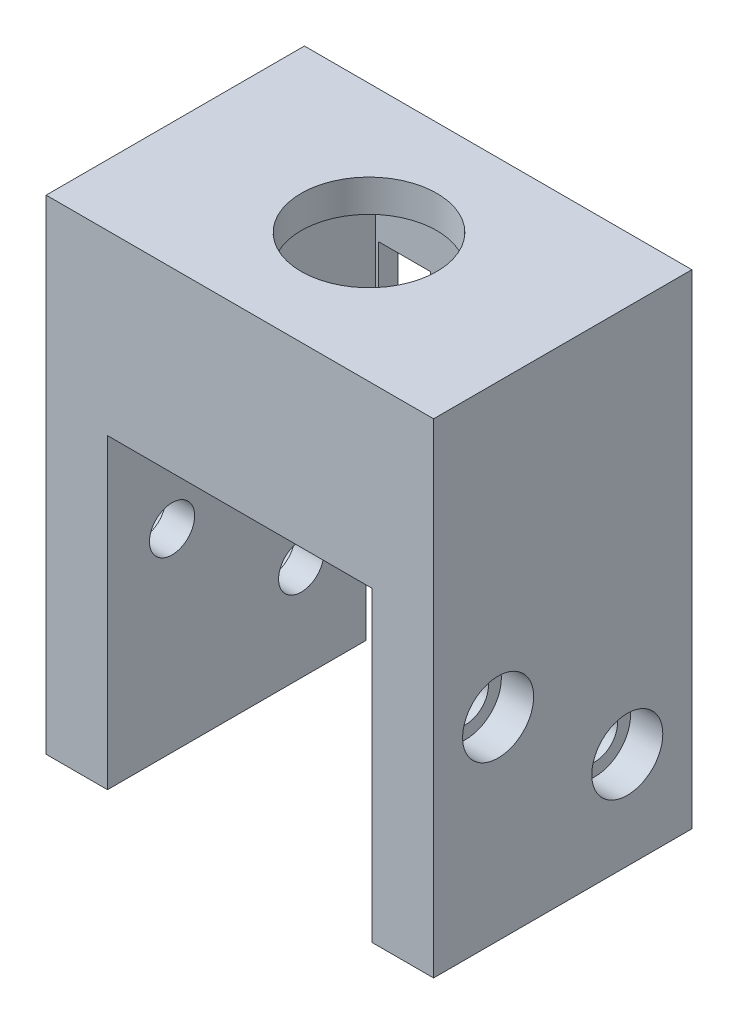
SolidWorks part; units mm, degrees
ref_plane "前视基准面" through (0, 0, 0) normal (0, 0, 1) x (1, 0, 0)
ref_plane "上视基准面" through (0, 0, 0) normal (0, 1, 0) x (1, 0, 0)
ref_plane "右视基准面" through (0, 0, 0) normal (1, 0, 0) x (0, 0, -1)
other "Configuration Table"
sketch "草图1" plane through (0, 0, 0) normal (0, 1, 0) x (1, 0, 0)
  line L0 (-4.1, 0) -> (4.1, 0) construction
  line L1 (-4.1, -4) -> (4.1, -4)
  line L2 (-4.1, -4) -> (-4.1, 4)
  line L3 (-4.1, 4) -> (4.1, 4)
  line L4 (4.1, -4) -> (4.1, 4)
  line L10 (-4.1, 4) -> (-6, 4)
  line L11 (-4.1, 4) -> (-4.1, -4)
  line L12 (-4.1, -4) -> (-6, -4)
  line L13 (-6, 4) -> (-6, -4)
  line L14 (4.1, 4) -> (6, 4)
  line L15 (4.1, 4) -> (4.1, -4)
  line L16 (4.1, -4) -> (6, -4)
  line L17 (6, 4) -> (6, -4)
  circle A0 centre (0, 0) radius 2.1
  dimension "D3" = 4.2
  dimension "D5" = 1.9
  dimension "D1" = 8
  dimension "D2" = 4
  dimension "D4" = 8.2
extrude "凸台-拉伸1" add sketch "草图1" along normal blind 1 contours L2 L3 L4 L1 | A0
extrude "凸台-拉伸2" add sketch "草图1<6>" against normal blind 15 from surface separate body contours L10 L13 L12 L2 L11 | L17 L14 L15 L4 L16 region at (-5.05, 0, 0) region at (5.05, 0, 0) starting at face at (0, 1, 0)
sketch "草图1<6>" plane through (0, 0, 0) normal (0, 1, 0) x (1, 0, 0) same geometry as "草图1"
sketch "草图2" plane through (0, 0, 0) normal (0, -1, 0) x (1, 0, 0)
  line L0 (4.1, -4) -> (4.1, 4) construction
  line L1 (4.1, 3.4) -> (-4.1, 3.4)
  line L2 (4.1, 3.4) -> (4.1, 4)
  line L3 (4.1, 4) -> (-4.1, 4)
  line L4 (-4.1, 3.4) -> (-4.1, 4)
  line L5 (-4.1, 4) -> (4.1, 4) construction
  line L6 (-4.1, -4) -> (-4.1, 4) construction
  line L7 (4.1, -3.4) -> (-4.1, -3.4)
  line L8 (4.1, -3.4) -> (4.1, -4)
  line L9 (4.1, -4) -> (-4.1, -4)
  line L10 (-4.1, -3.4) -> (-4.1, -4)
  line L12 (-4.1, 4) -> (-3.2, 4)
  line L13 (-4.1, 4) -> (-4.1, -4)
  line L14 (-4.1, -4) -> (-3.2, -4)
  line L15 (-3.2, 4) -> (-3.2, -4)
  line L16 (4.1, 4) -> (3.2, 4)
  line L17 (4.1, 4) -> (4.1, -4)
  line L18 (4.1, -4) -> (3.2, -4)
  line L19 (3.2, 4) -> (3.2, -4)
  line M14 (4.1, 4) -> (-4.1, 4)
  line M15 (-4.1, 4) -> (-4.1, -4)
  line M16 (-4.1, -4) -> (4.1, -4)
  line M17 (4.1, -4) -> (4.1, 4)
  dimension "D1" = 0.6
  dimension "D2" = 0.9
extrude "凸台-拉伸3" add sketch "草图2" along normal blind 4.5 contours L15 L3 L1 M15 | L19 L3 L15 L1 | L19 L1 M14 M17 | L1 L19 L7 M17 | L7 L19 M16 M17 | L19 L7 L15 L9 | L15 L7 M15 M16 | L15 L1 L7 M15 region at (3.65, 0, 0) region at (3.65, 0, 3.7) region at (0, 0, 3.7) region at (3.65, 0, -3.7) region at (-3.65, 0, 0) region at (-3.65, 0, 3.7) region at (0, 0, -3.7) region at (-3.65, 0, -3.7)
sketch "草图3" plane through (0, 0, -4) normal (0, 0, -1) x (-1, 0, 0)
  line L0 (4.1, -4.5) -> (-4.1, -4.5) construction
  line L1 (-3.1, -4.5) -> (-1.5, -4.5)
  line L2 (-3.1, -4.5) -> (-3.1, -2.5)
  line L3 (-3.1, -2.5) -> (-1.5, -2.5)
  line L4 (-1.5, -4.5) -> (-1.5, -2.5)
  line L5 (-4.1, -14) -> (-4.1, -4.5) construction
  line L6 (1.5, -4.5) -> (3.1, -4.5)
  line L7 (1.5, -4.5) -> (1.5, -2.5)
  line L8 (1.5, -2.5) -> (3.1, -2.5)
  line L9 (3.1, -4.5) -> (3.1, -2.5)
  line L10 (4.1, -14) -> (4.1, -4.5) construction
  line M13 (-4.1, -4.5) -> (4.1, -4.5)
  dimension "D1" = 2
  dimension "D2" = 1
  dimension "D3" = 1
  dimension "D4" = 1.6
extrude "切除-拉伸1" cut sketch "草图3" against normal up to next contours L4 L3 L2 M13 | L9 L8 L7 M13 region at (2.3, -3.5, -4) region at (-2.3, -3.5, -4)
sketch "草图4" plane through (6, 0, 0) normal (1, 0, 0) x (0, 0, -1)
  line L0 (-4, -14) -> (4, -14) construction
  line L1 (-4, -14) -> (-4, 1) construction
  line L2 (4, -14) -> (4, 1) construction
  circle A0 centre (-2, -8) radius 1.1
  circle A1 centre (-2, -8) radius 0.7
  circle A2 centre (2, -11) radius 1.1
  circle A3 centre (2, -11) radius 0.7
  dimension "D1" = 1.4
  dimension "D2" = 2.2
  dimension "D3" = 6
  dimension "D4" = 3
  dimension "D5" = 2
  dimension "D6" = 2
extrude "切除-拉伸2" cut sketch "草图4" against normal through all contours A1 | A3
extrude "切除-拉伸3" cut sketch "草图4<3>" against normal blind 1 contours A0 | A2
sketch "草图4<3>" plane through (6, 0, 0) normal (1, 0, 0) x (0, 0, -1) same geometry as "草图4"
extrude "切除-拉伸4" cut sketch "草图4<4>" along normal blind 1 from surface contours A0 | A2 starting at face at (-6, -8, 1.3)
sketch "草图4<4>" plane through (6, 0, 0) normal (1, 0, 0) x (0, 0, -1) same geometry as "草图4"
